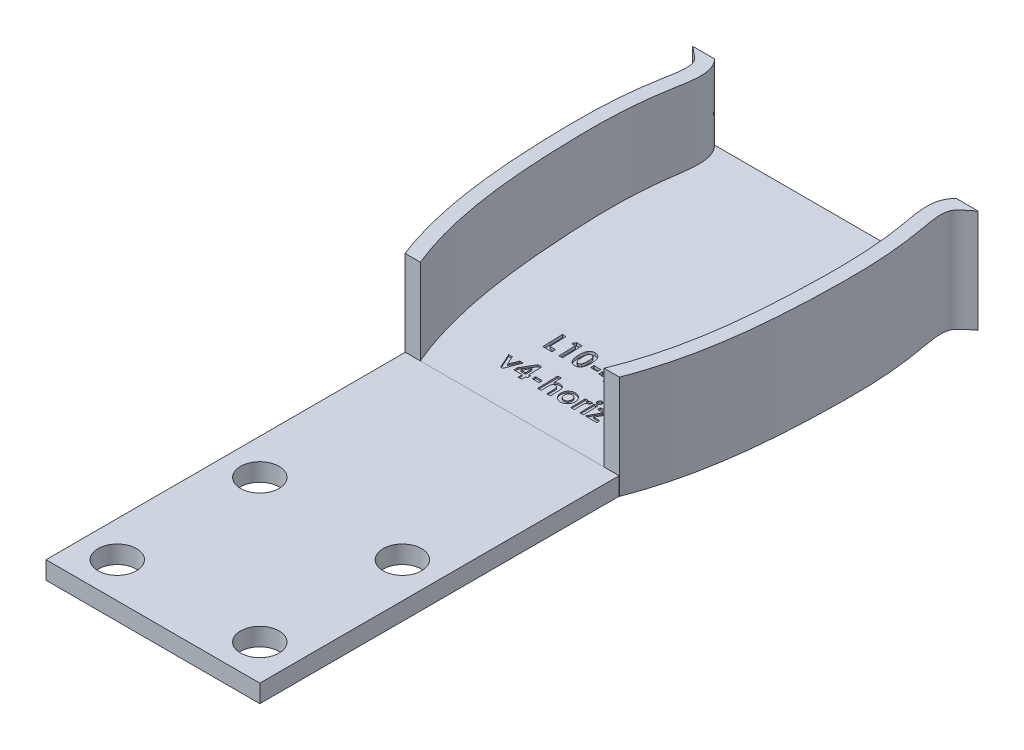
SolidWorks part; units mm, degrees
ref_plane "Front Plane" through (0, 0, 0) normal (0, 0, 1) x (1, 0, 0)
ref_plane "Top Plane" through (0, 0, 0) normal (0, 1, 0) x (1, 0, 0)
ref_plane "Right Plane" through (0, 0, 0) normal (1, 0, 0) x (0, 0, -1)
sketch "Sketch1" plane through (0, 0, 0) normal (0, 1, 0) x (1, 0, 0)
  line L0 (0, 0) -> (0, 27.6542) construction
  line L1 (-22.7965, -3.2766) -> (0, -3.2766)
  line L2 (-14.4907, -92.456) -> (0, -92.456)
  line L3 (-16.0362, -94.996) -> (0, -94.996)
  line L4 (-23.4734, -0.7366) -> (0, -0.7366)
  line L5 (0, -92.456) -> (0, -94.996)
  line L6 (0, -0.7366) -> (0, -3.2766)
  spline S0 degree 3 poles (-22.7965, -3.2766) (-28.943, -6.8029) (-26.6412, -16.3699) (-27.2056, -27.562) (-18.8723, -30.7915) (-21.7575, -42.9961) (-22.0006, -62.4867) (-20.2224, -81.3798) (-14.4907, -92.456) knots 0 0 0 0 0.208498 0.255193 0.340987 0.424768 0.602385 1 1 1 1
  spline S1 degree 1 poles (-23.4734, -0.7366) (-16.0362, -94.996) knots 0 0 1 1 construction
  spline S2 degree 3 poles (-16.0362, -94.996) (-16.2667, -94.5507) (-16.7207, -93.6824) (-17.6834, -91.7674) (-19.1575, -88.4222) (-20.8646, -83.4698) (-22.3225, -77.3976) (-23.3041, -71.2506) (-23.9054, -65.1074) (-24.214, -59.025) (-24.3544, -53.1181) (-24.2722, -48.1367) (-23.9537, -43.9987) (-23.63, -41.3407) (-23.2773, -39.1317) (-22.9749, -37.5006) (-22.7392, -36.0192) (-22.6398, -34.7303) (-22.7166, -33.7311) (-22.8977, -33.1875) (-23.0807, -32.8731) (-23.418, -32.4452) (-24.1373, -31.7792) (-25.3452, -30.8514) (-26.7197, -29.7579) (-27.8747, -28.5832) (-28.6792, -27.3414) (-29.2728, -25.9014) (-29.5204, -24.2439) (-29.5402, -22.4746) (-29.5412, -20.9757) (-29.6087, -19.393) (-29.6989, -17.7671) (-29.822, -15.5523) (-29.9098, -12.7307) (-29.6657, -9.3304) (-28.899, -6.5263) (-27.7455, -4.4088) (-26.7714, -3.1903) (-25.8398, -2.3097) (-25.1946, -1.8025) (-24.6454, -1.4272) (-24.2814, -1.2005) (-23.9957, -1.0362) (-23.7726, -0.9083) (-23.5912, -0.8042) (-23.4734, -0.7366) knots -0.006639 -0.006639 -0.006639 -0.006639 0.009347 0.025332 0.057303 0.121244 0.185186 0.249127 0.313069 0.37701 0.440952 0.504893 0.536864 0.568835 0.58482 0.600805 0.616791 0.632776 0.648762 0.664747 0.67274 0.680732 0.696718 0.712703 0.728688 0.744674 0.752666 0.760659 0.776645 0.79263 0.808615 0.824601 0.840586 0.856571 0.888542 0.920513 0.952484 0.968469 0.984454 0.992447 1.00044 1.004436 1.008432 1.010431 1.012429 1.016425 1.016425 1.016425 1.016425
  point P1 (-25.0063, -5.08)
  point P2 (-14.4907, -92.456)
  point P4 (-27.0002, -21.6408)
  point P6 (-20.0279, -75.438)
  point P7 (-26.4795, -25.9842)
  point P8 (-22.7965, -3.2766)
  point P18 (-20.828, -31.6992)
  point P19 (-20.7645, -39.5478)
  point P20 (-21.7297, -56.1594)
  dimension "D1" = 5.08
  dimension "D2" = 50.0126
  dimension "D3" = 21.6408
  dimension "D4" = 54.0004
  dimension "D5" = 25.9842
  dimension "D6" = 52.959
  dimension "D7" = 31.6992
  dimension "D8" = 41.656
  dimension "D9" = 39.5478
  dimension "D10" = 41.529
  dimension "D11" = 56.1594
  dimension "D12" = 43.4594
  dimension "D13" = 75.438
  dimension "D14" = 40.0558
  dimension "D15" = 92.456
  dimension "D16" = 28.9814
  dimension "D17" = 3.2766
  dimension "D18" = 45.593
  dimension "D19" = 2.54
extrude "Boss-Extrude1" add sketch "Sketch1" along normal blind 15.24
mirror "Mirror1" about plane through (0, 0, 0) normal (1, 0, 0) of "Boss-Extrude1"
sketch "Sketch3" plane through (0, 0, 0) normal (0, 1, 0) x (1, 0, 0)
  line L2 (-16.0362, -94.996) -> (16.0362, -94.996)
  line L3 (23.4734, -0.7366) -> (-23.4734, -0.7366)
  line L4 (-16.0362, -94.996) -> (16.0362, -94.996)
  line L5 (23.4734, -0.7366) -> (-23.4734, -0.7366)
  spline S2 degree 3 poles (-873.8929, -2959.7934) (9.44, -90.1714) (6.2643, -114.4817) (17.6834, -91.7674) (19.1575, -88.4222) (20.8646, -83.4698) (22.3225, -77.3976) (23.3041, -71.2506) (23.9054, -65.1074) (24.214, -59.025) (24.3544, -53.1181) (24.2722, -48.1367) (23.9537, -43.9987) (23.63, -41.3407) (23.2773, -39.1317) (22.9749, -37.5006) (22.7392, -36.0192) (22.6398, -34.7303) (22.7166, -33.7311) (22.8977, -33.1875) (23.0807, -32.8731) (23.418, -32.4452) (24.1373, -31.7792) (25.3452, -30.8514) (26.7197, -29.7579) (27.8747, -28.5832) (28.6792, -27.3414) (29.2728, -25.9014) (29.5204, -24.2439) (29.5402, -22.4746) (29.5412, -20.9757) (29.6087, -19.393) (29.6989, -17.7671) (29.822, -15.5523) (29.9098, -12.7307) (29.6657, -9.3304) (28.899, -6.5263) (27.7455, -4.4088) (26.7714, -3.1903) (25.8398, -2.3097) (25.1946, -1.8025) (24.6454, -1.4272) (24.2814, -1.2005) (23.9957, -1.0362) (16.5226, 3.2473) (-18.5383, 23.6119) (2614.6575, -1511.3109) knots -0.701112 -0.701112 -0.701112 -0.701112 0.009347 0.025332 0.057303 0.121244 0.185186 0.249127 0.313069 0.37701 0.440952 0.504893 0.536864 0.568835 0.58482 0.600805 0.616791 0.632776 0.648762 0.664747 0.67274 0.680732 0.696718 0.712703 0.728688 0.744674 0.752666 0.760659 0.776645 0.79263 0.808615 0.824601 0.840586 0.856571 0.888542 0.920513 0.952484 0.968469 0.984454 0.992447 1.00044 1.004436 1.008432 1.010431 1.012429 1.27614 1.27614 1.27614 1.27614 only from (16.0362, -94.996) to (23.4734, -0.7366)
  spline S3 degree 3 poles (-2614.8674, -1511.4333) (18.5401, 23.613) (-16.5224, 3.2475) (-23.9957, -1.0362) (-24.2814, -1.2005) (-24.6454, -1.4272) (-25.1946, -1.8025) (-25.8398, -2.3097) (-26.7714, -3.1903) (-27.7455, -4.4088) (-28.899, -6.5263) (-29.6657, -9.3304) (-29.9098, -12.7307) (-29.822, -15.5523) (-29.6989, -17.7671) (-29.6087, -19.393) (-29.5412, -20.9757) (-29.5402, -22.4746) (-29.5204, -24.2439) (-29.2728, -25.9014) (-28.6792, -27.3414) (-27.8747, -28.5832) (-26.7197, -29.7579) (-25.3452, -30.8514) (-24.1373, -31.7792) (-23.418, -32.4452) (-23.0807, -32.8731) (-22.8977, -33.1875) (-22.7166, -33.7311) (-22.6398, -34.7303) (-22.7392, -36.0192) (-22.9749, -37.5006) (-23.2773, -39.1317) (-23.63, -41.3407) (-23.9537, -43.9987) (-24.2722, -48.1367) (-24.3544, -53.1181) (-24.214, -59.025) (-23.9054, -65.1074) (-23.3041, -71.2506) (-22.3225, -77.3976) (-20.8646, -83.4698) (-19.1575, -88.4222) (-17.6834, -91.7674) (-6.2645, -114.4814) (-9.4399, -90.172) (873.8586, -2959.6822) knots -0.266361 -0.266361 -0.266361 -0.266361 -0.002642 -0.000644 0.001354 0.005351 0.009347 0.01734 0.025332 0.041318 0.057303 0.089274 0.121244 0.153215 0.169201 0.185186 0.201171 0.217157 0.233142 0.249127 0.25712 0.265113 0.281098 0.297083 0.313069 0.329054 0.337047 0.34504 0.361025 0.37701 0.392996 0.408981 0.424966 0.440952 0.472923 0.504893 0.568835 0.632776 0.696718 0.760659 0.824601 0.888542 0.952484 0.984454 1.00044 1.710889 1.710889 1.710889 1.710889 only from (-23.4734, -0.7366) to (-16.0362, -94.996)
  spline S4 degree 3 poles (16.0362, -94.996) (16.2667, -94.5507) (16.7207, -93.6824) (17.6834, -91.7674) (19.1575, -88.4222) (20.8646, -83.4698) (22.3225, -77.3976) (23.3041, -71.2506) (23.9054, -65.1074) (24.214, -59.025) (24.3544, -53.1181) (24.2722, -48.1367) (23.9537, -43.9987) (23.63, -41.3407) (23.2773, -39.1317) (22.9749, -37.5006) (22.7392, -36.0192) (22.6398, -34.7303) (22.7166, -33.7311) (22.8977, -33.1875) (23.0807, -32.8731) (23.418, -32.4452) (24.1373, -31.7792) (25.3452, -30.8514) (26.7197, -29.7579) (27.8747, -28.5832) (28.6792, -27.3414) (29.2728, -25.9014) (29.5204, -24.2439) (29.5402, -22.4746) (29.5412, -20.9757) (29.6087, -19.393) (29.6989, -17.7671) (29.822, -15.5523) (29.9098, -12.7307) (29.6657, -9.3304) (28.899, -6.5263) (27.7455, -4.4088) (26.7714, -3.1903) (25.8398, -2.3097) (25.1946, -1.8025) (24.6454, -1.4272) (24.2814, -1.2005) (23.9957, -1.0362) (23.7726, -0.9083) (23.5912, -0.8042) (23.4734, -0.7366) knots -0.006639 -0.006639 -0.006639 -0.006639 0.009347 0.025332 0.057303 0.121244 0.185186 0.249127 0.313069 0.37701 0.440952 0.504893 0.536864 0.568835 0.58482 0.600805 0.616791 0.632776 0.648762 0.664747 0.67274 0.680732 0.696718 0.712703 0.728688 0.744674 0.752666 0.760659 0.776645 0.79263 0.808615 0.824601 0.840586 0.856571 0.888542 0.920513 0.952484 0.968469 0.984454 0.992447 1.00044 1.004436 1.008432 1.010431 1.012429 1.016425 1.016425 1.016425 1.016425
  spline S5 degree 3 poles (-23.4734, -0.7366) (-23.5912, -0.8042) (-23.7726, -0.9083) (-23.9957, -1.0362) (-24.2814, -1.2005) (-24.6454, -1.4272) (-25.1946, -1.8025) (-25.8398, -2.3097) (-26.7714, -3.1903) (-27.7455, -4.4088) (-28.899, -6.5263) (-29.6657, -9.3304) (-29.9098, -12.7307) (-29.822, -15.5523) (-29.6989, -17.7671) (-29.6087, -19.393) (-29.5412, -20.9757) (-29.5402, -22.4746) (-29.5204, -24.2439) (-29.2728, -25.9014) (-28.6792, -27.3414) (-27.8747, -28.5832) (-26.7197, -29.7579) (-25.3452, -30.8514) (-24.1373, -31.7792) (-23.418, -32.4452) (-23.0807, -32.8731) (-22.8977, -33.1875) (-22.7166, -33.7311) (-22.6398, -34.7303) (-22.7392, -36.0192) (-22.9749, -37.5006) (-23.2773, -39.1317) (-23.63, -41.3407) (-23.9537, -43.9987) (-24.2722, -48.1367) (-24.3544, -53.1181) (-24.214, -59.025) (-23.9054, -65.1074) (-23.3041, -71.2506) (-22.3225, -77.3976) (-20.8646, -83.4698) (-19.1575, -88.4222) (-17.6834, -91.7674) (-16.7207, -93.6824) (-16.2667, -94.5507) (-16.0362, -94.996) knots -0.006639 -0.006639 -0.006639 -0.006639 -0.002642 -0.000644 0.001354 0.005351 0.009347 0.01734 0.025332 0.041318 0.057303 0.089274 0.121244 0.153215 0.169201 0.185186 0.201171 0.217157 0.233142 0.249127 0.25712 0.265113 0.281098 0.297083 0.313069 0.329054 0.337047 0.34504 0.361025 0.37701 0.392996 0.408981 0.424966 0.440952 0.472923 0.504893 0.568835 0.632776 0.696718 0.760659 0.824601 0.888542 0.952484 0.984454 1.00044 1.016425 1.016425 1.016425 1.016425
  dimension "D1" = 0
extrude "Boss-Extrude2" add sketch "Sketch3" against normal blind 3.175
sketch "Sketch4" plane through (0, 0, 0) normal (0, 1, 0) x (1, 0, 0)
  line L1 (-34.3632, 7.3821) -> (33.0011, 7.3821)
  line L2 (-34.3632, 7.3821) -> (-34.3632, -6.6723)
  line L3 (-34.3632, -6.6723) -> (33.0011, -6.6723)
  line L4 (33.0011, 7.3821) -> (33.0011, -6.6723)
extrude "Cut-Extrude1" cut sketch "Sketch4" against normal through all both and the other way through all
sketch "Sketch5" plane through (0, 0, 0) normal (0, 1, 0) x (1, 0, 0)
  line L1 (-25.9901, -88.3745) -> (23.66, -88.3745)
  line L2 (-25.9901, -88.3745) -> (-25.9901, -99.7274)
  line L3 (-25.9901, -99.7274) -> (23.66, -99.7274)
  line L4 (23.66, -88.3745) -> (23.66, -99.7274)
extrude "Cut-Extrude2" cut sketch "Sketch5" against normal through all both and the other way through all
sketch "Sketch6" plane through (0, 0, 0) normal (1, 0, 0) x (0, 0, -1)
  line L0 (-88.3745, -3.175) -> (-6.6723, -3.175)
  line L1 (-6.6723, -3.175) -> (-6.6723, 2.54)
  line L2 (-6.6723, 15.24) -> (-6.6723, -3.175) construction
  line L4 (-88.3745, -3.175) -> (-88.3745, 0)
  line L5 (-88.3745, -3.175) -> (-88.3745, 15.24) construction
  line L7 (-88.3745, 0) -> (-13.0223, 2.54)
  line L8 (-13.0223, 2.54) -> (-6.6723, 2.54)
  dimension "D1" = 3.175
  dimension "D2" = 5.715
  dimension "D3" = 6.35
extrude "Boss-Extrude3" add sketch "Sketch6" along normal up to surface and the other way up to surface up to face at (18.7955, 7.62, 67.9489) other way up to face at (-18.7955, 7.62, 67.9489)
sketch "Sketch7" plane through (0, 2.54, 0) normal (0, 1, 0) x (1, 0, 0)
  line L0 (-27.3161, -75.6745) -> (27.3161, -75.6745) construction
  line L1 (-16.3712, -88.3745) -> (16.3712, -88.3745) construction
  text T0 "<b>L10-4V</b>\r\n<b>v4-horiz</b>" font "Century Gothic" height 3.5
  dimension "D1" = 12.7
extrude "Cut-Extrude3" cut sketch "Sketch7" against normal blind 2.54
sketch "Sketch11" plane through (0, 0, 0) normal (0, 1, 0) x (1, 0, 0)
  line L1 (19.05, -63.5) -> (19.05, -152.4)
  line L2 (19.05, -63.5) -> (-19.05, -63.5)
  line L3 (-19.05, -63.5) -> (-19.05, -152.4)
  line L4 (19.05, -152.4) -> (-19.05, -152.4)
  circle A0 centre (12.7, -146.05) radius 3.429
  circle A1 centre (12.7, -120.65) radius 3.429
  circle A2 centre (-12.7, -120.65) radius 3.429
  circle A3 centre (-12.7, -146.05) radius 3.429
  point P4 (0, -63.5)
  dimension "D3" = 6.858
  dimension "D1" = 38.1
  dimension "D2" = 88.9
  dimension "D4" = 6.35
  dimension "D5" = 6.35
  dimension "D8" = 63.5
  dimension "D6" = 2
  dimension "D7" = 2
extrude "Boss-Extrude6" add sketch "Sketch11" against normal up to surface (3.175 mm away) up to face at (-0.2819, -3.175, 39.8356)
sketch "Sketch12" plane through (0, 0, 0) normal (0, 1, 0) x (1, 0, 0)
  line L0 (19.1036, -88.3745) -> (16.3712, -88.3745) construction
  line L1 (-63.441, -30.7902) -> (49.3604, -30.7902)
  line L2 (-63.441, -30.7902) -> (-63.441, -6.6723)
  line L3 (-63.441, -6.6723) -> (49.3604, -6.6723)
  line L4 (49.3604, -30.7902) -> (49.3604, -6.6723)
  line L5 (26.0684, -6.6723) -> (28.8413, -6.6723) construction
  dimension "D1" = 57.5843
extrude "Cut-Extrude4" cut sketch "Sketch12" against normal through all both and the other way through all
